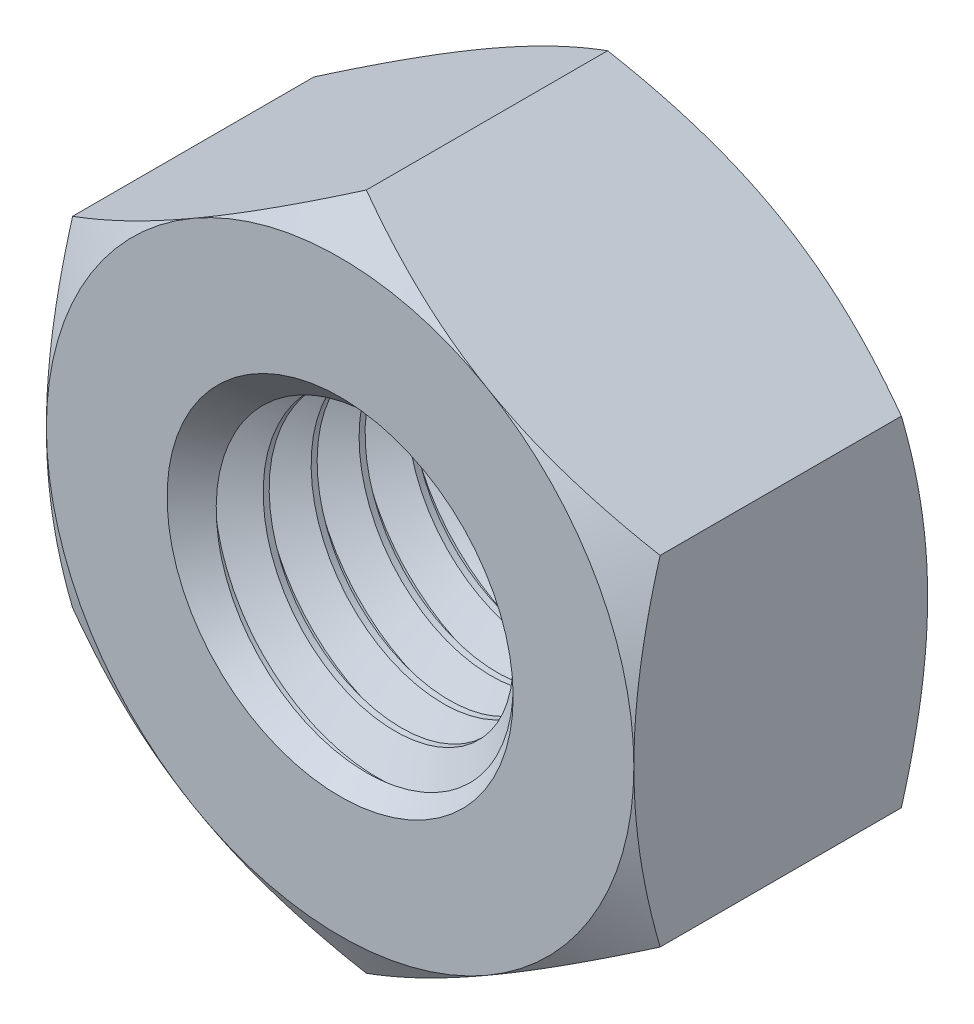
SolidWorks part; units mm, degrees
ref_plane "Front Plane" through (0, 0, 0) normal (0, 0, 1) x (1, 0, 0)
ref_plane "Top Plane" through (0, 0, 0) normal (0, 1, 0) x (1, 0, 0)
ref_plane "Right Plane" through (0, 0, 0) normal (1, 0, 0) x (0, 0, -1)
sketch "Sketch1" plane through (0, 0, 0) normal (0, 0, 1) x (1, 0, 0)
  line L1 (0, 6.4158) -> (-5.5563, 3.2079)
  line L2 (-5.5563, 3.2079) -> (-5.5563, -3.2079)
  line L3 (-5.5563, -3.2079) -> (0, -6.4158)
  line L4 (0, -6.4158) -> (5.5562, -3.2079)
  line L5 (5.5562, -3.2079) -> (5.5562, 3.2079)
  line L6 (5.5562, 3.2079) -> (0, 6.4158)
  circle A0 centre (0, 0) radius 5.5563 construction
  dimension "Width" = 11.1125
sketch "Sketch2" plane through (0, 0, 0) normal (1, 0, 0) x (0, 0, -1)
  line L0 (-2.7781, 0) -> (2.7781, 0) construction
  line L1 (-2.7781, 0) -> (-2.7781, 3.175)
  line L2 (-2.7781, 3.175) -> (2.7781, 3.175)
  line L3 (2.7781, 3.175) -> (2.7781, 0)
  line L4 (2.7214, 3.2732) -> (3.175, 2.4876) construction
  line L5 (3.175, 2.4876) -> (3.6286, 3.2732) construction
  line L6 (3.6286, 3.2732) -> (2.7214, 3.2732) construction
  line L7 (2.7498, 3.2241) -> (3.6002, 3.2241)
  line L8 (3.6002, 3.2241) -> (3.2317, 2.5858)
  line L9 (3.2317, 2.5858) -> (3.1183, 2.5858)
  line L10 (3.1183, 2.5858) -> (2.7498, 3.2241)
  line L11 (3.175, 2.5858) -> (3.175, 2.4876) construction
  line L12 (2.7781, 3.175) -> (3.5719, 3.175) construction
  line L13 (3.175, 3.2732) -> (3.175, 3.175) construction
  line L14 (-2.7781, -3.175) -> (2.7781, -3.175)
  line L15 (0, 5.5563) -> (0, -5.5563) construction
  line L16 (0, 5.5563) -> (0, -5.5563)
  point P2 (0, 0)
  point P18 (3.175, 3.2241)
  point P22 (-2.7781, -3.175)
  point P23 (-2.7781, 5.5563)
  point P24 (2.7781, 5.5563)
  dimension "Thread Size" = 6.35
  dimension "Thread Pitch" = 0.9071
  dimension "D2" = 0.1134
  dimension "Height" = 5.5562
sketch "Sketch3" plane through (0, 0, 0) normal (0, 0, 1) x (1, 0, 0)
  line L0 (5.5562, 3.2079) -> (0, 6.4158) construction
  line L1 (5.5562, -3.2079) -> (5.5562, 3.2079) construction
  line L2 (0, -6.4158) -> (5.5562, -3.2079) construction
  line L3 (-5.5563, -3.2079) -> (0, -6.4158) construction
  line L4 (-5.5563, 3.2079) -> (-5.5563, -3.2079) construction
  line L5 (0, 6.4158) -> (-5.5563, 3.2079) construction
  line L6 (5.5562, 3.2079) -> (0, 6.4158)
  line L7 (5.5562, -3.2079) -> (5.5562, 3.2079)
  line L8 (0, -6.4158) -> (5.5562, -3.2079)
  line L9 (-5.5563, -3.2079) -> (0, -6.4158)
  line L10 (-5.5563, 3.2079) -> (-5.5563, -3.2079)
  line L11 (0, 6.4158) -> (-5.5563, 3.2079)
extrude "Boss-Extrude1" add sketch "Sketch3" along normal up to vertex (2.7781 mm away) from vertex up to point (0, 0, 2.7781) starting at point (0, 0, -2.7781)
sketch "Sketch4" plane through (0, 0, 2.7781) normal (0, 0, 1) x (1, 0, 0)
  circle A0 centre (0, 0) radius 5.5563 construction
  circle A1 centre (0, 0) radius 5.5563
extrude "Cut-Extrude1" cut sketch "Sketch4" against normal through all draft 60 flip side to cut
sketch "Sketch5" plane through (0, 0, -2.7781) normal (0, 0, -1) x (-1, 0, 0)
  circle A0 centre (0, 0) radius 5.5563 construction
  circle A1 centre (0, 0) radius 5.5563
extrude "Cut-Extrude2" cut sketch "Sketch5" against normal through all draft 60 flip side to cut
sketch "Sketch6" plane through (0, 0, 0) normal (1, 0, 0) x (0, 0, -1)
  line L1 (-2.7781, 0) -> (2.7781, 0)
  line L2 (-2.7781, 0) -> (-2.7781, 3.175)
  line L3 (-2.7781, 3.175) -> (2.7781, 3.175)
  line L4 (2.7781, 0) -> (2.7781, 3.175)
revolve "Cut-Revolve1" cut sketch "Sketch6" angle 360 about L1
sketch "Sketch7" plane through (0, 0, -2.7781) normal (0, 0, -1) x (-1, 0, 0)
  circle A0 centre (0, 0) radius 3.175 construction
  circle A1 centre (0, 0) radius 3.175
curve "Helix/Spiral1" pitch 0.9071 height 6.4634 radius 3.175 centre (0, 0, -2.7781) axis (0, 0, 1) start towards (0, 1, 0)
sketch "Sketch8" plane through (0, 0, 0) normal (1, 0, 0) x (0, 0, -1)
  line L0 (2.7498, 3.2241) -> (3.6002, 3.2241) construction
  line L1 (3.1183, 2.5858) -> (2.7498, 3.2241) construction
  line L2 (3.2317, 2.5858) -> (3.1183, 2.5858) construction
  line L3 (3.6002, 3.2241) -> (3.2317, 2.5858) construction
  line L4 (2.7498, 3.2241) -> (3.6002, 3.2241)
  line L5 (3.1183, 2.5858) -> (2.7498, 3.2241)
  line L6 (3.2317, 2.5858) -> (3.1183, 2.5858)
  line L7 (3.6002, 3.2241) -> (3.2317, 2.5858)
sweep "Sweep1" add profiles "Sketch8" path "Helix/Spiral1"
sketch "Sketch9" plane through (0, 0, -2.7781) normal (0, 0, -1) x (-1, 0, 0)
  circle A0 centre (0, 0) radius 3.2732
extrude "Cut-Extrude3" cut sketch "Sketch9" against normal through all draft 45 and the other way through all
sketch "Sketch10" plane through (0, 0, 2.7781) normal (0, 0, 1) x (1, 0, 0)
  circle A1 centre (0, 0) radius 3.2732
  circle A2 centre (0, 0) radius 3.2732
  dimension "D1" = 0
extrude "Cut-Extrude4" cut sketch "Sketch10" against normal through all draft 45 and the other way through all
equation "\"D2@Sketch2\" = \"Thread Pitch@Sketch2\" / 8"
equation "\"D4@Helix/Spiral1\" = \"Thread Pitch@Sketch2\""
equation "\"D3@Helix/Spiral1\"= \"Height@Sketch2\" + \"Thread Pitch@Sketch2\""
